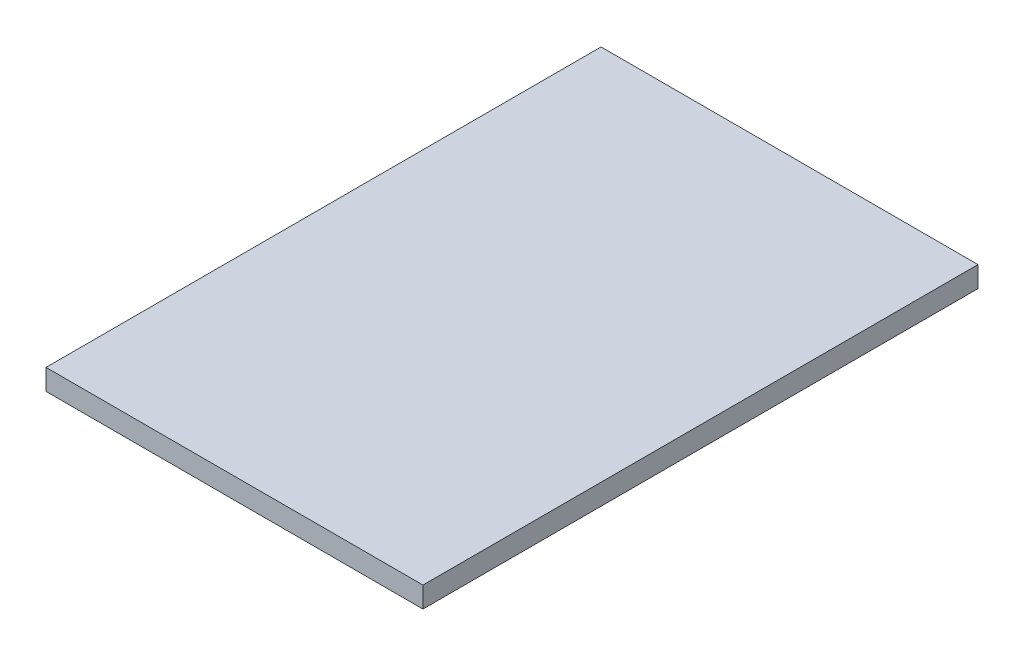
SolidWorks part; units mm, degrees
material "Perspex (TM) GS Acrylic Cast Sheet"
ref_plane "Front Plane" through (0, 0, 0) normal (0, 0, 1) x (1, 0, 0)
ref_plane "Top Plane" through (0, 0, 0) normal (0, 1, 0) x (1, 0, 0)
ref_plane "Right Plane" through (0, 0, 0) normal (1, 0, 0) x (0, 0, -1)
sketch "Sketch1" plane through (0, 0, 0) normal (0, 1, 0) x (1, 0, 0)
  line L1 (-81.5, -120) -> (81.5, -120)
  line L2 (-81.5, -120) -> (-81.5, 120)
  line L3 (-81.5, 120) -> (81.5, 120)
  line L4 (81.5, -120) -> (81.5, 120)
  line L5 (-81.5, -120) -> (81.5, 120) construction
  line L6 (-81.5, 120) -> (81.5, -120) construction
  point P0 (0, 0)
  dimension "D1" = 163
  dimension "D2" = 240
extrude "Boss-Extrude1" add sketch "Sketch1" along normal blind 9
sketch "Sketch2" plane through (0, 9, 0) normal (0, 1, 0) x (1, 0, 0)
  line L14 (-72.5, -111) -> (72.5, -111)
  line L15 (72.5, -111) -> (72.5, 111)
  line L16 (72.5, 111) -> (-72.5, 111)
  line L17 (-72.5, 111) -> (-72.5, -111)
  line L18 (-72.5, -111) -> (72.5, -111)
  line L19 (72.5, -111) -> (72.5, 111)
  line L20 (72.5, 111) -> (-72.5, 111)
  line L21 (-72.5, 111) -> (-72.5, -111)
  dimension "D1" = 9
equation "\"PCLength\"= 145mm'Length across I/O from PS to GPU"
equation "\"PCWidth\"= 340mm'Distance of longest part parallel to GPU(ussually GPU)"
equation "\"PCHeight\"= 180mm'Tallest point with mobo laying flat"
equation "\"WallThickness\"= 9mm'Thickness of each outer tank wall"
equation "\"ThermoBarrierThickness\"= 6mm'Thickness of barrier between hot side and cold side"
equation "\"HotSideGap\"= 36mm'Space in the hot side for a pump"
equation "\"PCClearance\"= 40mm'Clearance from top of tank to top of PC"
equation "\"RadiatorHeight\"= 277.37mm'Final Height from ground of radiators"
equation "\"AirflowGap\"= 25mm'Distance between radiators and tank for airflow"
equation "\"VolumeSubtraction\"= 230mm"
equation "\"D1@Sketch1\"=\"PCLength\" + (2 * \"WallThickness\")"
equation "\"D1@Boss-Extrude1\"=\"WallThickness\""
equation "\"D2@Sketch1\"=\"PCHeight\" + \"ThermoBarrierThickness\" + \"HotSideGap\" + (2 * \"WallThickness\")"
